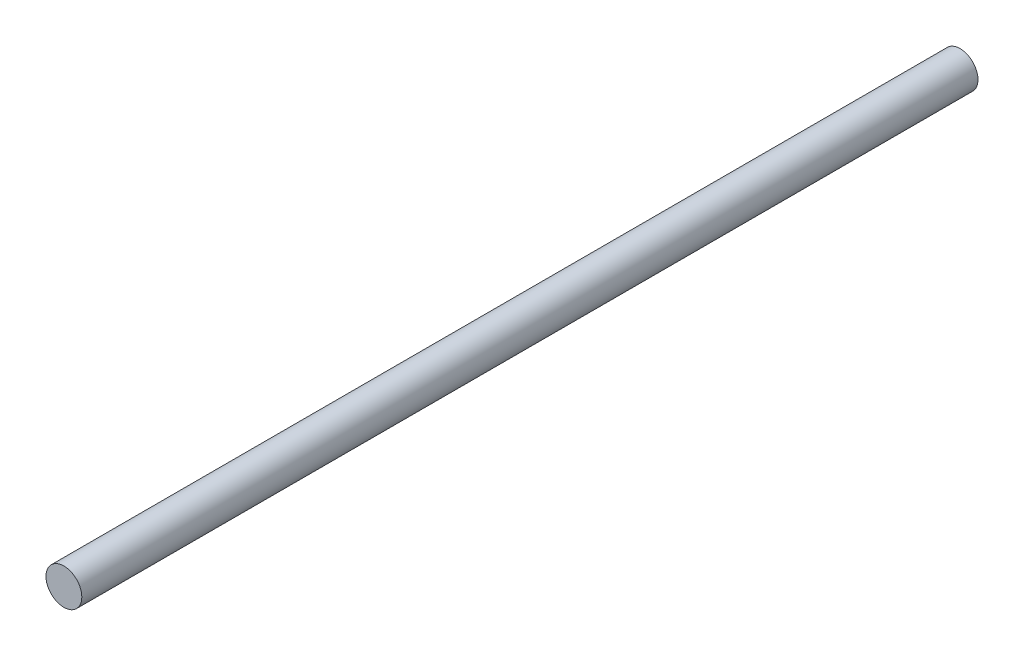
SolidWorks part; units mm, degrees
ref_plane "Front Plane" through (0, 0, 0) normal (0, 0, 1) x (1, 0, 0)
ref_plane "Top Plane" through (0, 0, 0) normal (0, 1, 0) x (1, 0, 0)
ref_plane "Right Plane" through (0, 0, 0) normal (1, 0, 0) x (0, 0, -1)
sketch "Sketch1" plane through (0, 0, 0) normal (0, 0, 1) x (1, 0, 0)
  circle A0 centre (0, 0) radius 5.08
  dimension "D1" = 10.16
extrude "Boss-Extrude1" add sketch "Sketch1" along normal blind 254
